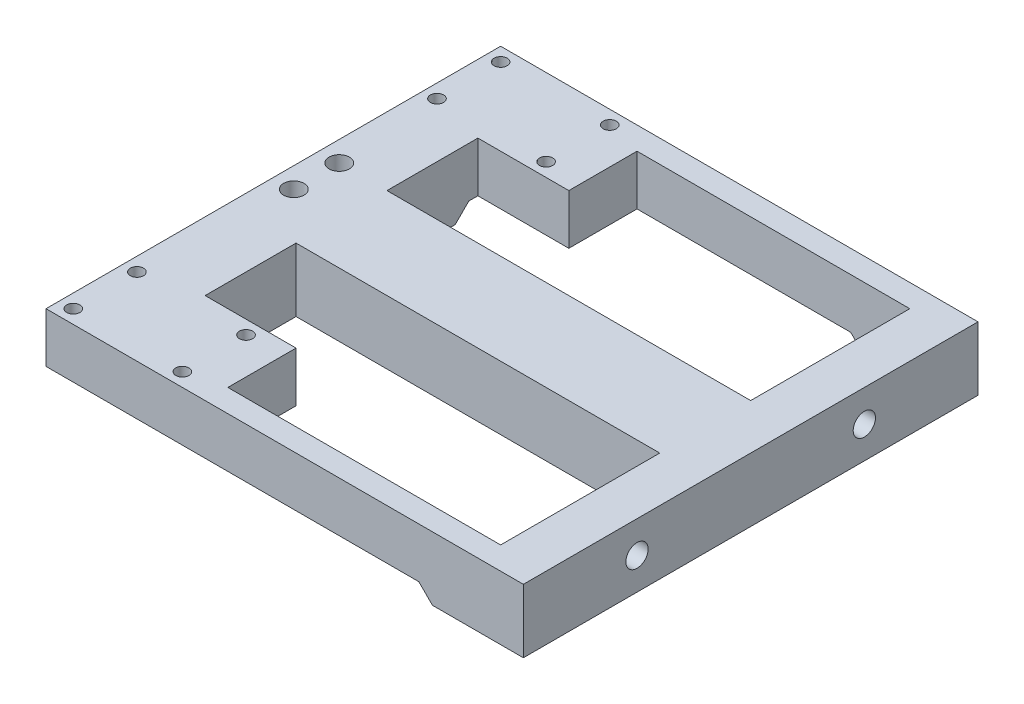
SolidWorks part; units mm, degrees
ref_plane "前视基准面" through (0, 0, 0) normal (0, 0, 1) x (1, 0, 0)
ref_plane "上视基准面" through (0, 0, 0) normal (0, 1, 0) x (1, 0, 0)
ref_plane "右视基准面" through (0, 0, 0) normal (1, 0, 0) x (0, 0, -1)
other "Configuration Table"
sketch "草图1" plane through (0, 0, 0) normal (0, 1, 0) x (1, 0, 0)
  line L1 (0, 0) -> (-105, 0)
  line L2 (0, 0) -> (0, 100)
  line L3 (0, 100) -> (-105, 100)
  line L4 (-105, 0) -> (-105, 100)
  dimension "D1" = 100
  dimension "D2" = 105
extrude "凸台-拉伸1" add sketch "草图1" along normal blind 16
sketch "草图6" plane through (0, 16, 0) normal (0, 1, 0) x (1, 0, 0)
  line L0 (-105, 100) -> (-105, 0) construction
  line L1 (-45.2241, 40) -> (-5, 40)
  line L2 (-70, 20) -> (-70, 5)
  line L3 (-70, 5) -> (-5, 5)
  line L4 (-5, 40) -> (-5, 5)
  line L5 (0, 0) -> (0, 100) construction
  line L6 (-105, 0) -> (0, 0) construction
  line L7 (-105, 50) -> (-60.5255, 50) construction
  line L8 (-70, 95) -> (-5, 95)
  line L9 (-5, 60) -> (-5, 95)
  line L10 (-45.2241, 60) -> (-5, 60)
  line L11 (-70, 80) -> (-70, 95)
  line L12 (-70, 80) -> (-100, 80)
  line L13 (-45.2241, 40) -> (-100, 40)
  line L15 (-70, 20) -> (-100, 20)
  line L16 (-100, 40) -> (-100, 20)
  line L17 (-45.2241, 60) -> (-100, 60)
  line L18 (-100, 60) -> (-100, 80)
  dimension "D1" = 35
  dimension "D2" = 5
  dimension "D3" = 5
  dimension "D4" = 20
  dimension "D5" = 30
  dimension "D6" = 20
extrude "切除-拉伸5" cut sketch "草图6" against normal up to next
sketch "草图8" plane through (0, 16, 0) normal (0, 1, 0) x (1, 0, 0)
  line L0 (-105, 100) -> (-102, 100) construction
  line L1 (0, 100) -> (-105, 100) construction
  line L2 (-102, 100) -> (-102, 97) construction
  line L3 (-102, 97) -> (-78, 97) construction
  line L4 (-78, 97) -> (-78, 83) construction
  line L5 (-78, 83) -> (-102, 83) construction
  line L6 (-105, 50) -> (-51.1245, 50) construction
  line L7 (-105, 100) -> (-105, 0) construction
  line L8 (-78, 17) -> (-102, 17) construction
  line L9 (-78, 3) -> (-78, 17) construction
  line L10 (-102, 3) -> (-78, 3) construction
  line L11 (-102, 0) -> (-102, 3) construction
  line L12 (-105, 0) -> (-102, 0) construction
  circle A0 centre (-102, 97) radius 1.45
  circle A1 centre (-102, 83) radius 1.45
  circle A2 centre (-78, 97) radius 1.45
  circle A3 centre (-78, 83) radius 1.45
  circle A4 centre (-78, 17) radius 1.45
  circle A5 centre (-78, 3) radius 1.45
  circle A6 centre (-102, 17) radius 1.45
  circle A7 centre (-102, 3) radius 1.45
  dimension "D6" = 2.9
  dimension "D7" = 2.9
  dimension "D8" = 2.9
  dimension "D9" = 2.9
  dimension "D1" = 3
  dimension "D2" = 3
  dimension "D3" = 24
  dimension "D4" = 14
  dimension "D5" = 24
extrude "切除-拉伸7" cut sketch "草图8" against normal through all
sketch "草图9" plane through (-5, 0, 0) normal (-1, 0, 0) x (0, 0, 1)
  line L0 (-40, 0) -> (-5, 0) construction
  line L1 (-5, 0) -> (-5, 16) construction
  line L2 (-5, 16) -> (-40, 16) construction
  line L3 (-40, 16) -> (-40, 0) construction
  line L4 (-95, 0) -> (-60, 0) construction
  line L5 (-60, 0) -> (-60, 16) construction
  line L6 (-60, 16) -> (-95, 16) construction
  line L7 (-95, 16) -> (-95, 0) construction
  line L8 (-40, 0) -> (-5, 0)
  line L9 (-5, 0) -> (-5, 16)
  line L10 (-5, 16) -> (-40, 16)
  line L11 (-40, 16) -> (-40, 0)
  line L12 (-95, 0) -> (-60, 0)
  line L13 (-60, 0) -> (-60, 16)
  line L14 (-60, 16) -> (-95, 16)
  line L15 (-95, 16) -> (-95, 0)
extrude "凸台-拉伸2" add sketch "草图9" along normal blind 5
sketch "草图12" plane through (-100, 0, 0) normal (1, 0, 0) x (0, 0, -1)
  line L0 (20, 0) -> (40, 0) construction
  line L1 (40, 0) -> (40, 16) construction
  line L2 (40, 16) -> (20, 16) construction
  line L3 (20, 16) -> (20, 0) construction
  line L4 (60, 0) -> (80, 0) construction
  line L5 (80, 0) -> (80, 16) construction
  line L6 (80, 16) -> (60, 16) construction
  line L7 (60, 16) -> (60, 0) construction
  line L8 (20, 0) -> (40, 0)
  line L9 (40, 0) -> (40, 16)
  line L10 (40, 16) -> (20, 16)
  line L11 (20, 16) -> (20, 0)
  line L12 (60, 0) -> (80, 0)
  line L13 (80, 0) -> (80, 16)
  line L14 (80, 16) -> (60, 16)
  line L15 (60, 16) -> (60, 0)
extrude "凸台-拉伸3" add sketch "草图12" along normal blind 10
sketch "草图13" plane through (0, 16, 0) normal (0, 1, 0) x (1, 0, 0)
  line L0 (-105, 50) -> (-100.5, 50) construction
  line L1 (-105, 100) -> (-105, 0) construction
  line L3 (-100.5, 50) -> (-100.5, 60) construction
  circle A0 centre (-100.5, 50) radius 2.25
  circle A1 centre (-100.5, 60) radius 2.25
  dimension "D4" = 4.5
  dimension "D5" = 4.5
  dimension "D3" = 10
  dimension "D6" = 4.5
  dimension "D1" = 4.5
  dimension "D2" = 10
extrude "切除-拉伸10" cut sketch "草图13" against normal blind 5
sketch "草图14" plane through (0, 0, 0) normal (0, -1, 0) x (1, 0, 0)
  line L4 (0, -100) -> (0, 0)
  line L5 (0, 0) -> (-105, 0)
  line L6 (-105, 0) -> (-105, -100)
  line L7 (-105, -100) -> (0, -100)
  line L9 (0, 0) -> (-105, 0)
  line L10 (-105, 0) -> (-105, -100)
  line L11 (-105, -100) -> (0, -100)
  line L13 (0, -100) -> (0, 0)
  dimension "D1" = 0
extrude "切除-拉伸11" cut sketch "草图14" against normal blind 2
sketch "草图16" plane through (0, 2, 0) normal (0, -1, 0) x (1, 0, 0)
  line L0 (-10, -40) -> (-10, -5) construction
  line L1 (-105, 0) -> (-20, 0)
  line L2 (-105, 0) -> (-105, -25)
  line L3 (-105, -25) -> (-20, -25)
  line L4 (-20, 0) -> (-20, -25)
  line L5 (-20, -75) -> (-105, -75)
  line L6 (-20, -75) -> (-20, -100)
  line L7 (-20, -100) -> (-105, -100)
  line L8 (-105, -75) -> (-105, -100)
  line L9 (-10, -95) -> (-10, -60) construction
  dimension "D1" = 10
  dimension "D2" = 10
extrude "切除-拉伸13" cut sketch "草图16" against normal blind 3
chamfer "倒角1" distance 3 angle 45 4 edges at (-20, 5, -2.5) (-97.5, 5, -25) (-97.5, 5, -75) (-20, 5, -97.5)
sketch "草图17" plane through (-105, 0, 0) normal (-1, 0, 0) x (0, 0, 1)
  line L0 (0, 9) -> (-55.4, 9) construction
  line L1 (0, 16) -> (0, 5) construction
  line L2 (-100, 16) -> (0, 16) construction
  circle A0 centre (-55.4, 9) radius 2.25
  dimension "D2" = 4.5
  dimension "D1" = 55.4
  dimension "D3" = 7
extrude "切除-拉伸14" cut sketch "草图17" against normal blind 5
sketch "草图18" plane through (-100, 0, 0) normal (-1, 0, 0) x (0, 0, 1)
  circle A0 centre (-55.4, 9) radius 1.5
  dimension "D1" = 3
extrude "切除-拉伸15" cut sketch "草图18" against normal blind 4
sketch "草图21" plane through (0, 0, 0) normal (1, 0, 0) x (0, 0, -1)
  line L0 (100, 16) -> (100, 2) construction
  line L1 (0, 16) -> (100, 16) construction
  line L2 (0, 16) -> (0, 2) construction
  circle A0 centre (25, 9) radius 2.45
  circle A1 centre (75, 9) radius 2.45
  dimension "D1" = 25
  dimension "D2" = 7
  dimension "D3" = 4.9
  dimension "D4" = 4.9
  dimension "D5" = 7
  dimension "D6" = 25
extrude "切除-拉伸17" cut sketch "草图21" against normal blind 13.2
